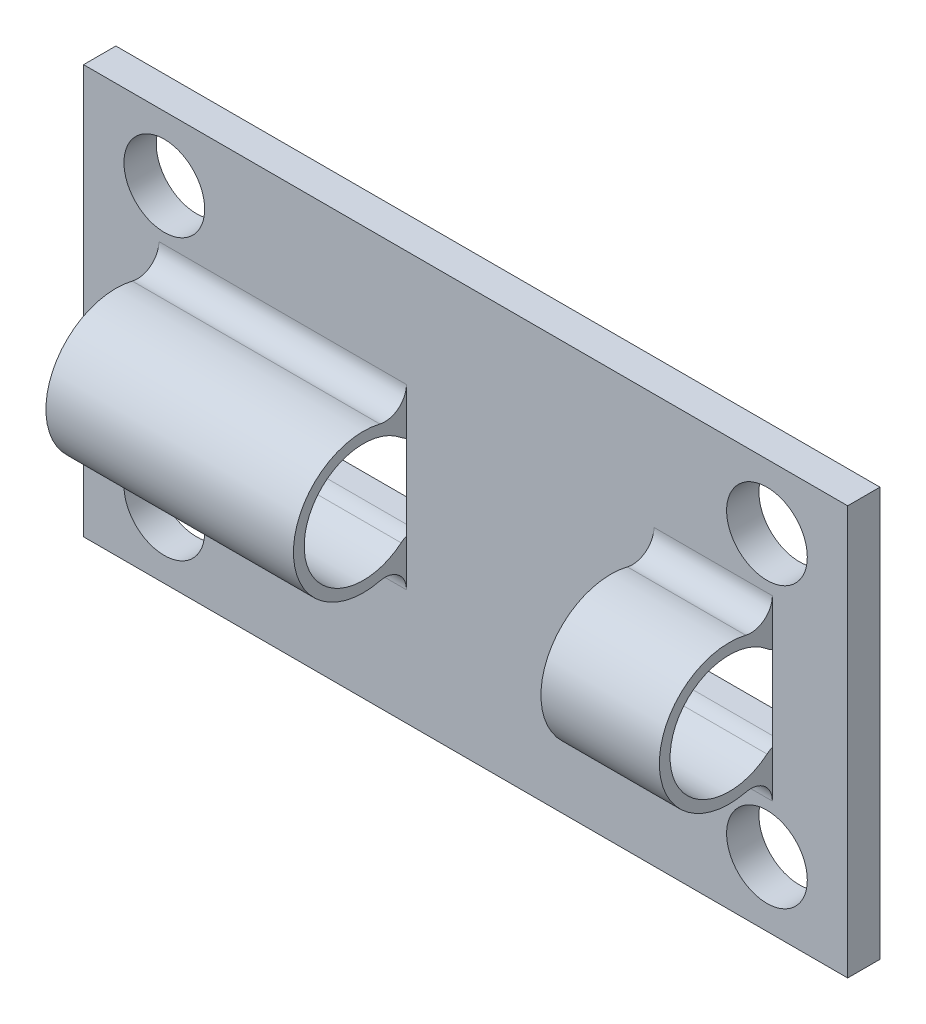
SolidWorks part; units mm, degrees
ref_plane "Front Plane" through (0, 0, 0) normal (0, 0, 1) x (1, 0, 0)
ref_plane "Top Plane" through (0, 0, 0) normal (0, 1, 0) x (1, 0, 0)
ref_plane "Right Plane" through (0, 0, 0) normal (1, 0, 0) x (0, 0, -1)
sketch "Sketch1" plane through (0, 0, 0) normal (0, 0, 1) x (1, 0, 0)
  line L1 (-35.5, -19) -> (35.5, -19)
  line L2 (-35.5, -19) -> (-35.5, 19)
  line L3 (-35.5, 19) -> (35.5, 19)
  line L4 (35.5, -19) -> (35.5, 19)
  line L5 (-35.5, -19) -> (35.5, 19) construction
  line L6 (-35.5, 19) -> (35.5, -19) construction
  circle A0 centre (-28, 13) radius 3.75
  circle A1 centre (28, 13) radius 3.75
  circle A2 centre (-28, -13) radius 3.75
  circle A3 centre (28, -13) radius 3.75
  point P0 (0, 0)
  point P14 (-16, -0.2346)
  point P19 (16, -0.2346)
  dimension "D5" = 7.5
  dimension "D6" = 2
  dimension "D8" = 7.5
  dimension "D9" = 7.5
  dimension "D1" = 71
  dimension "D2" = 38
  dimension "D3" = 6
  dimension "D4" = 7.5
  dimension "D7" = 7.5
  dimension "D10" = 7.5
  dimension "D11" = 6
  dimension "D12" = 6
extrude "Boss-Extrude1" add sketch "Sketch1" along normal blind 3 contours A0 | A1 | A2 | A3 | L1 L4 L3 L2 region at (-28, 13, 0) region at (28, 13, 0) region at (-28, -13, 0) region at (28, -13, 0)
sketch "Sketch3" plane through (35.5, 0, 0) normal (1, 0, 0) x (0, 0, -1)
  line L0 (-3, -19) -> (-3, 19) construction
  circle A1 centre (-7, 0) radius 6.5
  circle A2 centre (-7, 0) radius 5.5
  dimension "D1" = 13
  dimension "D2" = 11
  dimension "D3" = 4
extrude "Boss-Extrude2" add sketch "Sketch3" against normal blind 18
sketch "Sketch4" plane through (-35.5, 0, 0) normal (-1, 0, 0) x (0, 0, 1)
  circle A0 centre (7, 0) radius 5.5
  circle A1 centre (7, 0) radius 6.5
extrude "Boss-Extrude3" add sketch "Sketch4" against normal blind 30
sketch "Sketch5" plane through (0, 0, 3) normal (0, 0, 1) x (1, 0, 0)
  line L0 (-5.5, -3.7749) -> (-35.5, -3.7749) construction
  line L1 (-5.5, 3.7749) -> (-28.5, 3.7749)
  line L2 (-5.5, 3.7749) -> (-5.5, -3.7749)
  line L3 (-5.5, -3.7749) -> (-28.5, -3.7749)
  line L4 (-28.5, 3.7749) -> (-28.5, -3.7749)
  line L5 (35.5, -3.7749) -> (17.5, -3.7749) construction
  line L6 (17.5, 3.7749) -> (28.5, 3.7749)
  line L7 (17.5, 3.7749) -> (17.5, -3.7749)
  line L8 (17.5, -3.7749) -> (28.5, -3.7749)
  line L9 (28.5, 3.7749) -> (28.5, -3.7749)
  dimension "D1" = 23
  dimension "D2" = 11
extrude "Cut-Extrude2" cut sketch "Sketch5" against normal blind 30 contours L9 L7 L5 | L1 L4 L3 L2 region at (23, 0, 3)
sketch "Sketch6" plane through (-35.5, 0, 0) normal (-1, 0, 0) x (0, 0, 1)
  line L0 (3, 3.7749) -> (3, 5.1235)
  line L1 (3, -3.7749) -> (3, -5.1235)
  arc A0 (3, -5.1235) -> (3, 5.1235) centre (7, 0) ccw
  arc A1 (3, -3.7749) -> (3, 3.7749) centre (7, 0) ccw
extrude "Cut-Extrude3" cut sketch "Sketch6" against normal blind 7
sketch "Sketch7" plane through (35.5, 0, 0) normal (1, 0, 0) x (0, 0, -1)
  line L0 (-3, 5.1235) -> (-3, 3.7749)
  line L1 (-3, -3.7749) -> (-3, -5.1235)
  arc A0 (-3, 3.7749) -> (-3, -3.7749) centre (-7, 0) ccw
  arc A1 (-3, 5.1235) -> (-3, -5.1235) centre (-7, 0) ccw
extrude "Cut-Extrude4" cut sketch "Sketch7" against normal blind 7
fillet "Fillet2" radius 2 4 edges at (-17, -5.1235, 3) (23, -5.1235, 3) (-17, 5.1235, 3) (23, 5.1235, 3)
fillet "Fillet3" radius 2 4 edges at (-17, 3.7749, 3) (-17, -3.7749, 3) (23, -3.7749, 3) (23, 3.7749, 3)
